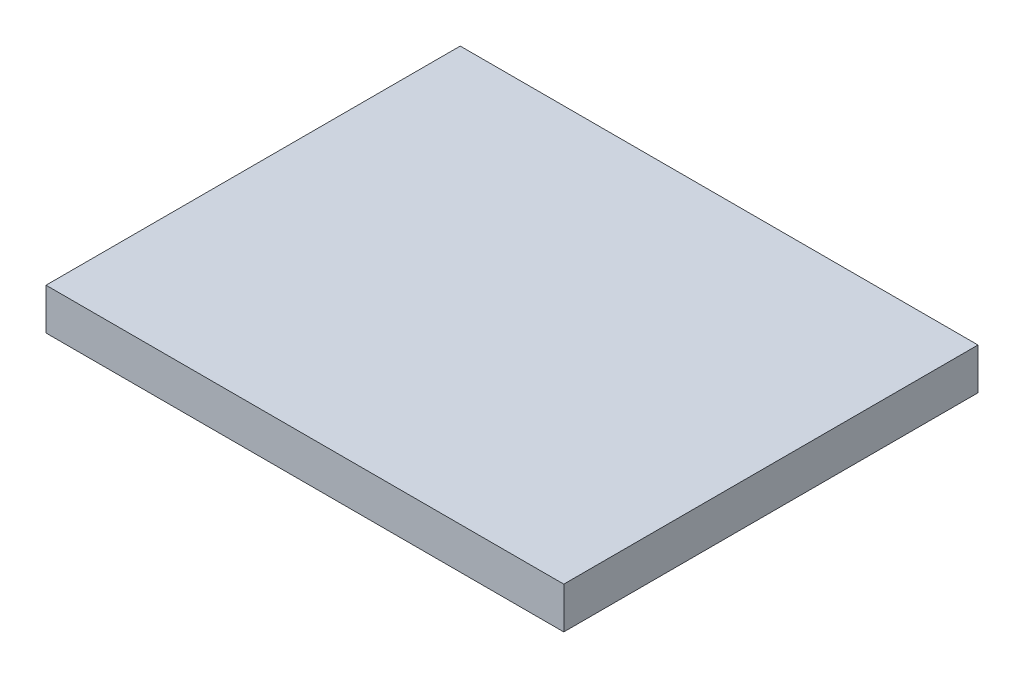
SolidWorks part; units mm, degrees
ref_plane "Front Plane" through (0, 0, 0) normal (0, 0, 1) x (1, 0, 0)
ref_plane "Top Plane" through (0, 0, 0) normal (0, 1, 0) x (1, 0, 0)
ref_plane "Right Plane" through (0, 0, 0) normal (1, 0, 0) x (0, 0, -1)
sketch "Sketch1" plane through (0, 0, 0) normal (0, 1, 0) x (1, 0, 0)
  line L5 (-250, -200) -> (250, -200)
  line L6 (-250, -200) -> (-250, 200)
  line L7 (-250, 200) -> (250, 200)
  line L8 (250, -200) -> (250, 200)
  line L9 (-250, -200) -> (250, 200) construction
  line L10 (-250, 200) -> (250, -200) construction
  point P0 (0, 0)
  dimension "D1" = 500
  dimension "D2" = 400
extrude "Boss-Extrude1" add sketch "Sketch1" along normal blind 40
